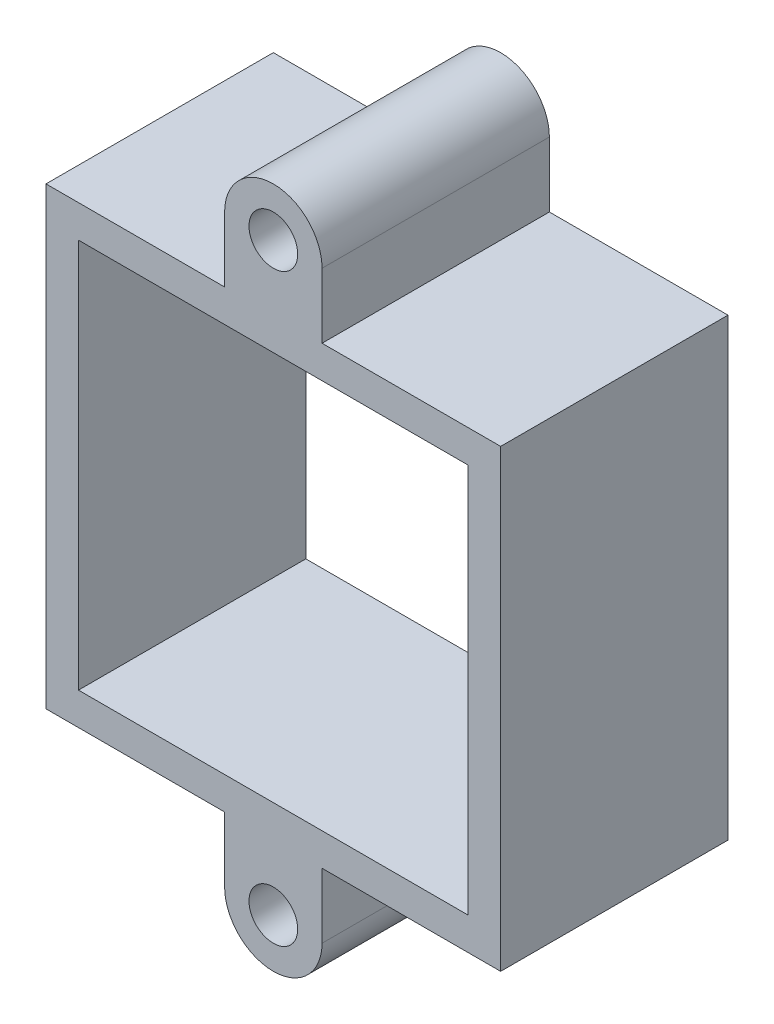
SolidWorks part; units mm, degrees
ref_plane "前视基准面" through (0, 0, 0) normal (0, 0, 1) x (1, 0, 0)
ref_plane "上视基准面" through (0, 0, 0) normal (0, 1, 0) x (1, 0, 0)
ref_plane "右视基准面" through (0, 0, 0) normal (1, 0, 0) x (0, 0, -1)
sketch "草图1" plane through (0, 0, 0) normal (0, 0, 1) x (1, 0, 0)
  line L0 (-7, 7) -> (7, 7)
  line L1 (-6, -6) -> (6, -6)
  line L2 (-6, -6) -> (-6, 6)
  line L3 (-6, 6) -> (6, 6)
  line L4 (6, -6) -> (6, 6)
  line L5 (-6, -6) -> (6, 6) construction
  line L6 (-6, 6) -> (6, -6) construction
  line L7 (7, -7) -> (7, 7)
  line L8 (-7, -7) -> (7, -7)
  line L9 (-7, -7) -> (-7, 7)
  point P0 (0, 0)
  dimension "D1" = 12
  dimension "D3" = 12
  dimension "D2" = 1
extrude "凸台-拉伸1" add sketch "草图1" along normal blind 7
sketch "草图2" plane through (0, -7, 0) normal (0, -1, 0) x (1, 0, 0)
  line L1 (-1.5, 0) -> (1.5, 0)
  line L2 (-1.5, 0) -> (-1.5, 7)
  line L3 (-1.5, 7) -> (1.5, 7)
  line L4 (1.5, 0) -> (1.5, 7)
  line L5 (-1.5, 0) -> (1.5, 7) construction
  line L6 (-1.5, 7) -> (1.5, 0) construction
  line L12 (-7, 7) -> (7, 7) construction
  line L13 (-7, 0) -> (7, 0) construction
  point P0 (0, 3.5)
  dimension "D1" = 3
extrude "凸台-拉伸2" add sketch "草图2" along normal blind 3.5
sketch "草图3" plane through (0, 0, 7) normal (0, 0, 1) x (1, 0, 0)
  line L0 (1.5, -10.5) -> (-1.5, -10.5) construction
  line L1 (-1.5, -10.5) -> (-1.5, -7) construction
  line L2 (1.5, -10.5) -> (1.5, -7) construction
  line L3 (-1.5, -9) -> (-1.5, -10.5)
  line L4 (-1.5, -10.5) -> (0, -10.5)
  line L5 (0, -10.5) -> (1.5, -10.5)
  line L6 (1.5, -10.5) -> (1.5, -9)
  circle A0 centre (0, -9) radius 1.5
  circle A1 centre (0, -9) radius 0.75
  line M5 (-1.5, -7) -> (-1.5, -10.5)
  line M6 (-1.5, -10.5) -> (1.5, -10.5)
  line M7 (1.5, -10.5) -> (1.5, -7)
  dimension "D1" = 1.5
extrude "切除-拉伸1" cut sketch "草图3" against normal through all contours A1 region at (0, -9, 7)
extrude "切除-拉伸2" cut sketch "草图3<3>" against normal through all contours A0 M5 M6 | A0 M6 M7 region at (-1.1649, -10.1649, 7) region at (1.1649, -10.1649, 7)
sketch "草图3<3>" plane through (0, 0, 7) normal (0, 0, 1) x (1, 0, 0) same geometry as "草图3"
mirror "镜向1" about plane through (0, 0, 0) normal (0, 1, 0) of "切除-拉伸1", "切除-拉伸2", "凸台-拉伸2"
sketch "草图6" plane through (0, 0, 7) normal (0, 0, 1) x (1, 0, 0)
  line L0 (-1.5, -9) -> (-1.5, -7) construction
  line L1 (1.5, -9) -> (1.5, -7) construction
  line L2 (1.5, -7) -> (7, -7) construction
  line L3 (7, -7) -> (7, 7) construction
  line L4 (7, 7) -> (1.5, 7) construction
  line L5 (1.5, 9) -> (1.5, 7) construction
  line L6 (-1.5, 9) -> (-1.5, 7) construction
  line L7 (-1.5, 7) -> (-7, 7) construction
  line L8 (-7, 7) -> (-7, -7) construction
  line L9 (-7, -7) -> (-1.5, -7) construction
  line L10 (-1.5, -9) -> (-1.5, -7)
  line L11 (1.5, -9) -> (1.5, -7)
  line L12 (1.5, -7) -> (7, -7)
  line L13 (7, -7) -> (7, 7)
  line L14 (7, 7) -> (1.5, 7)
  line L15 (1.5, 9) -> (1.5, 7)
  line L16 (-1.5, 9) -> (-1.5, 7)
  line L17 (-1.5, 7) -> (-7, 7)
  line L18 (-7, 7) -> (-7, -7)
  line L19 (-7, -7) -> (-1.5, -7)
  line L21 (5.25, -5.25) -> (-5.25, -5.25)
  line L22 (5.25, -5.25) -> (5.25, 5.25)
  line L23 (5.25, 5.25) -> (-5.25, 5.25)
  line L24 (-5.25, -5.25) -> (-5.25, 5.25)
  line L25 (5.25, -5.25) -> (-5.25, 5.25) construction
  line L26 (5.25, 5.25) -> (-5.25, -5.25) construction
  arc A0 (-1.5, -9) -> (1.5, -9) centre (0, -9) ccw construction
  arc A1 (1.5, 9) -> (-1.5, 9) centre (0, 9) ccw construction
  arc A2 (-1.5, -9) -> (1.5, -9) centre (0, -9) ccw
  arc A3 (1.5, 9) -> (-1.5, 9) centre (0, 9) ccw
  circle A4 centre (0, 9) radius 0.75 construction
  circle A5 centre (0, -9) radius 0.75 construction
  circle A6 centre (0, 9) radius 0.75
  circle A7 centre (0, -9) radius 0.75
  point P10 (0, 0)
  dimension "D1" = 10.5
  dimension "D2" = 10.5
